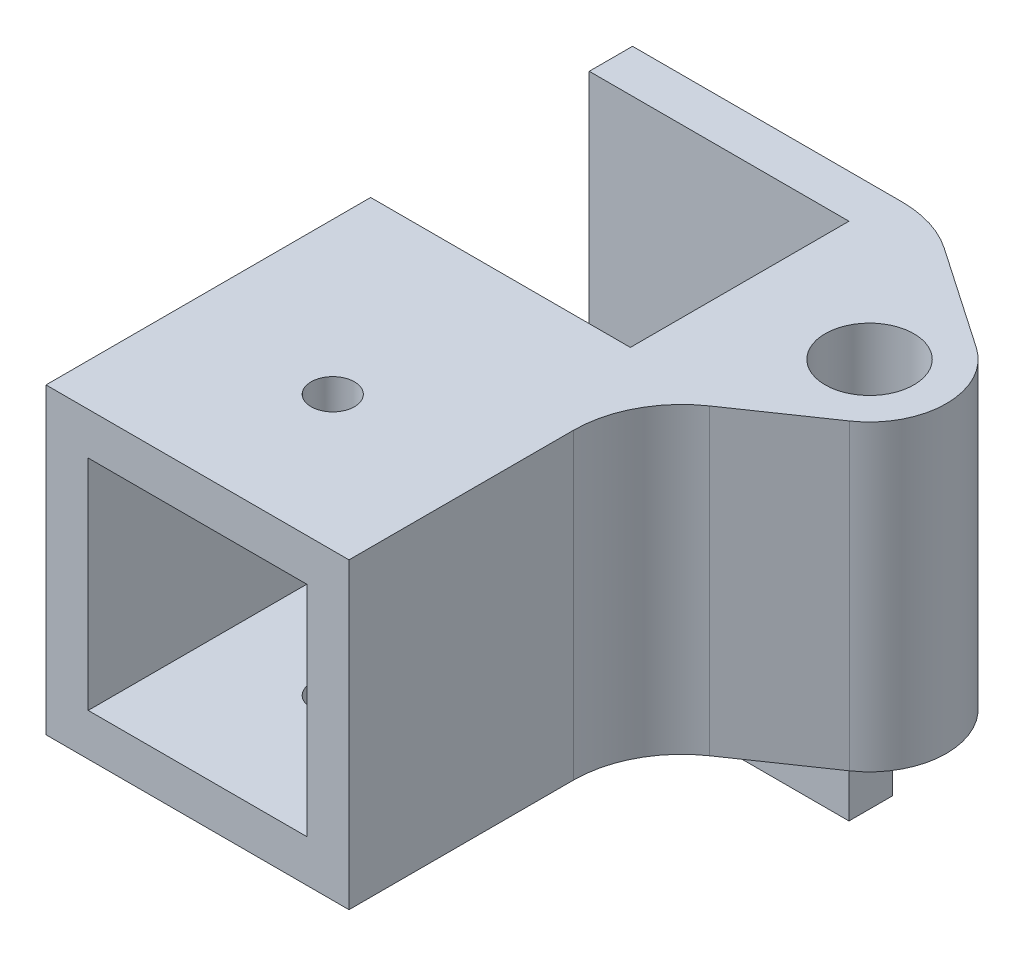
SolidWorks part; units mm, degrees
ref_plane "Front Plane" through (0, 0, 0) normal (0, 0, 1) x (1, 0, 0)
ref_plane "Top Plane" through (0, 0, 0) normal (0, 1, 0) x (1, 0, 0)
ref_plane "Right Plane" through (0, 0, 0) normal (1, 0, 0) x (0, 0, -1)
sketch "Sketch1" plane through (0, 0, 0) normal (0, 1, 0) x (1, 0, 0)
  line L0 (0, 54.2) -> (0, 50.2)
  line L1 (0, 50.2) -> (24, 50.2)
  line L2 (24, 50.2) -> (24, 30)
  line L3 (24, 30) -> (0, 30)
  line L4 (0, 30) -> (0, 0)
  line L5 (0, 0) -> (28, 0)
  line L6 (28, 0) -> (28, 54.2)
  line L7 (28, 54.2) -> (0, 54.2)
  line L8 (28, 54.2) -> (40.017, 45.9543)
  line L9 (40.017, 34.2457) -> (28, 26)
  arc A0 (40.017, 34.2457) -> (40.017, 45.9543) centre (36, 40.1) ccw
  circle A1 centre (36, 40.1) radius 4.1
  circle A2 centre (36, 40.1) radius 7.1 construction
  point P18 (24, 40.1)
  dimension "D6" = 8.2
  dimension "D1" = 4
  dimension "D2" = 4
  dimension "D4" = 20.2
  dimension "D3" = 30
  dimension "D5" = 28
  dimension "D7" = 3
  dimension "D8" = 8
  dimension "D9" = 55.544
  dimension "D10" = 55.544
extrude "Boss-Extrude1" add sketch "Sketch1" along normal blind 28 contours L6 A1 L9 A0 L8 | L6 L7 L0 L1 L2 L3 L4 L5 region at (14.9388, 0, -20.9978) region at (33.8275, 0, -49.8134)
sketch "Sketch2" plane through (0, 0, 0) normal (0, 0, 1) x (1, 0, 0)
  line L0 (14, 24.1) -> (14, 3.9) construction
  line L1 (3.9, 24.1) -> (24.1, 24.1)
  line L2 (3.9, 24.1) -> (3.9, 3.9)
  line L3 (3.9, 3.9) -> (24.1, 3.9)
  line L4 (24.1, 24.1) -> (24.1, 3.9)
  line L5 (24.1, 14) -> (3.9, 14) construction
  line L8 (0, 28) -> (0, 0) construction
  line L9 (28, 28) -> (28, 0) construction
  line L10 (0, 28) -> (0, 0) construction
  line L11 (0, 28) -> (0, 0)
  point P10 (0, 14)
  dimension "D1" = 20.2
extrude "Cut-Extrude1" cut sketch "Sketch2" against normal blind 25 contours L4 L1 L2 L3 region at (14, 14, 0)
sketch "Sketch3" plane through (0, 28, 0) normal (0, 1, 0) x (1, 0, 0)
  line L1 (3.9, 25) -> (24.1, 25) construction
  line L2 (14, 25) -> (14, 0) construction
  line L4 (3.9, 25) -> (24.1, 25)
  line L5 (0, 0) -> (28, 0) construction
  circle A0 centre (14, 12.5) radius 2
  dimension "D1" = 4
extrude "Cut-Extrude2" cut sketch "Sketch3" against normal through all contours A0
fillet "Fillet1" radius 10 2 edges at (28, 14, -54.2) (28, 14, -26)
sketch "Sketch4" plane through (0, 0, 0) normal (0, -1, 0) x (1, 0, 0)
  line L1 (0, -54.2) -> (24, -54.2)
  line L2 (0, -54.2) -> (0, -50.2)
  line L3 (0, -50.2) -> (24, -50.2)
  line L4 (24, -54.2) -> (24, -50.2)
  line L9 (12, -54.2) -> (12, -50.2) construction
  line M3 (0, -54.2) -> (24.8991, -54.2)
  line M14 (24, -50.2) -> (0, -50.2)
  line M15 (0, -50.2) -> (0, -54.2)
extrude "Boss-Extrude2" add sketch "Sketch4" along normal blind 20 contours L9 L3 M15 M3 | L9 L4 M3 M14 region at (12, 0, -52.2)
sketch "Sketch5" plane through (24, 0, 0) normal (1, 0, 0) x (0, 0, -1)
  line L0 (54.2, -8.6721) -> (54.2, -11.3279)
  line L1 (54.2, -11.3279) -> (51.9, -10)
  line L2 (51.9, -10) -> (54.2, -8.6721)
  line L3 (53.2, -9.2494) -> (53.2, -10.7506)
  line L4 (54.2, -20) -> (54.2, 0) construction
  point P7 (54.2, -10)
  point P8 (54.2, -10)
  line M6 (54.2, -20) -> (54.2, 0)
  dimension "D1" = 1
  dimension "D2" = 2.3
extrude "Cut-Extrude3" cut sketch "Sketch5" against normal through all contours L2 L3 L1 M6 | L3 L2 L1 region at (24, -10, -53.7463) region at (24, -10, -52.7667)
equation "\"local_angle\"=58.9479"
equation "\"D10@Sketch1\"= \"D9@Sketch1\""
